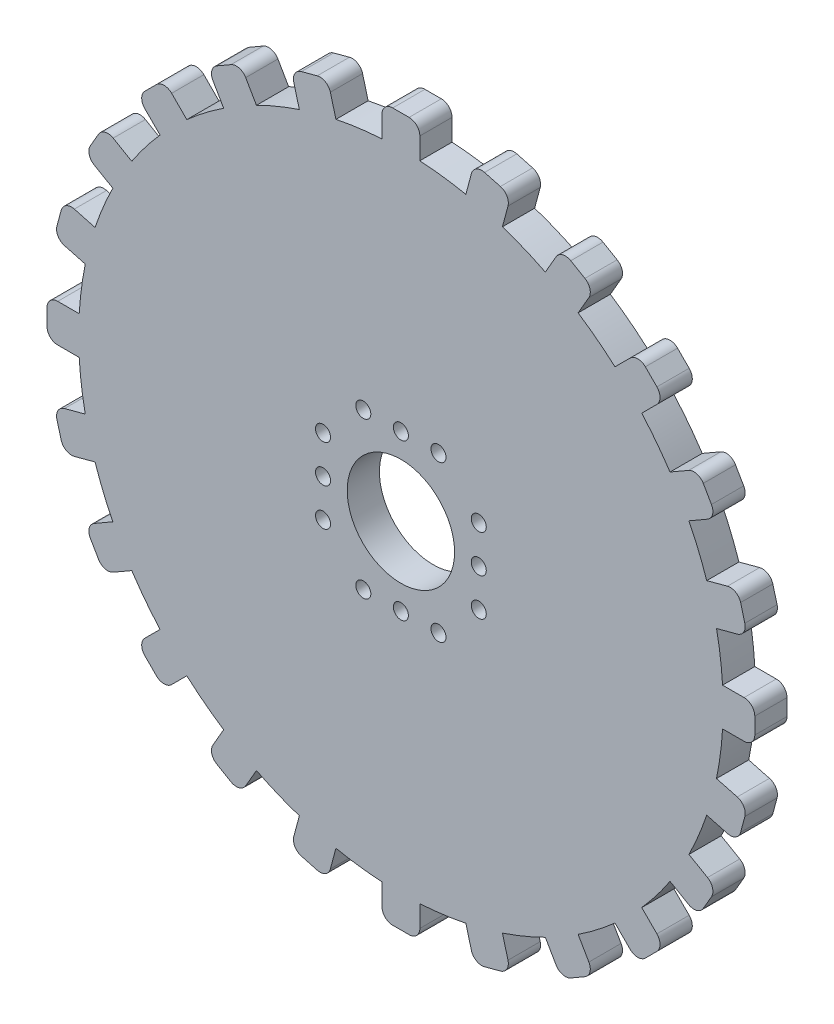
SolidWorks part; units mm, degrees
ref_plane "Front Plane" through (0, 0, 0) normal (0, 0, 1) x (1, 0, 0)
ref_plane "Top Plane" through (0, 0, 0) normal (0, 1, 0) x (1, 0, 0)
ref_plane "Right Plane" through (0, 0, 0) normal (1, 0, 0) x (0, 0, -1)
sketch "Sketch1" plane through (0, 0, 0) normal (0, 0, 1) x (1, 0, 0)
  circle A0 centre (0, 0) radius 30
  circle A1 centre (0, 0) radius 5
  circle A2 centre (-3.5, 7.25) radius 0.7
  circle A3 centre (0, 7.25) radius 0.7
  circle A4 centre (3.5, 7.25) radius 0.7
  circle A5 centre (7.25, 3.5) radius 0.7
  circle A6 centre (7.25, 0) radius 0.7
  circle A7 centre (7.25, -3.5) radius 0.7
  circle A8 centre (3.5, -7.25) radius 0.7
  circle A9 centre (0, -7.25) radius 0.7
  circle A10 centre (-3.5, -7.25) radius 0.7
  circle A11 centre (-7.25, -3.5) radius 0.7
  circle A12 centre (-7.25, 0) radius 0.7
  circle A13 centre (-7.25, 3.5) radius 0.7
  point P33 (0, 0)
  dimension "D1" = 60
  dimension "D2" = 10
  dimension "D4" = 1.4
  dimension "D3" = 4
extrude "Boss-Extrude1" add sketch "Sketch1" along normal blind 3
sketch "Sketch2" plane through (0, 0, 3) normal (0, 0, 1) x (1, 0, 0)
  line L0 (30, 0) -> (-30, 0) construction
  line L1 (0, 30) -> (0, -30) construction
  line L3 (29.9482, 1.7626) -> (31.9482, 1.7626)
  line L4 (29.9482, 1.7626) -> (29.9482, -1.7626)
  line L5 (29.9482, -1.7626) -> (31.9482, -1.7626)
  line L6 (32.9482, 0.7626) -> (32.9482, -0.7626)
  circle A0 centre (0, 0) radius 30 construction
  arc A1 (32.9482, -0.7626) -> (31.9482, -1.7626) centre (31.9482, -0.7626) cw
  arc A2 (31.9482, 1.7626) -> (32.9482, 0.7626) centre (31.9482, 0.7626) cw
  point P12 (29.9482, 0)
  point P17 (32.9482, 1.7626)
  dimension "D2" = 1
  dimension "D1" = 3
extrude "Boss-Extrude2" add sketch "Sketch2" against normal blind 3
ref_axis "Axis1" through (0, 0, -0.15) along (0, 0, 1)
pattern_circular "CirPattern2" count 24 every 15 about axis through (0, 0, -0.15) along (0, 0, 1) of "Boss-Extrude2"
